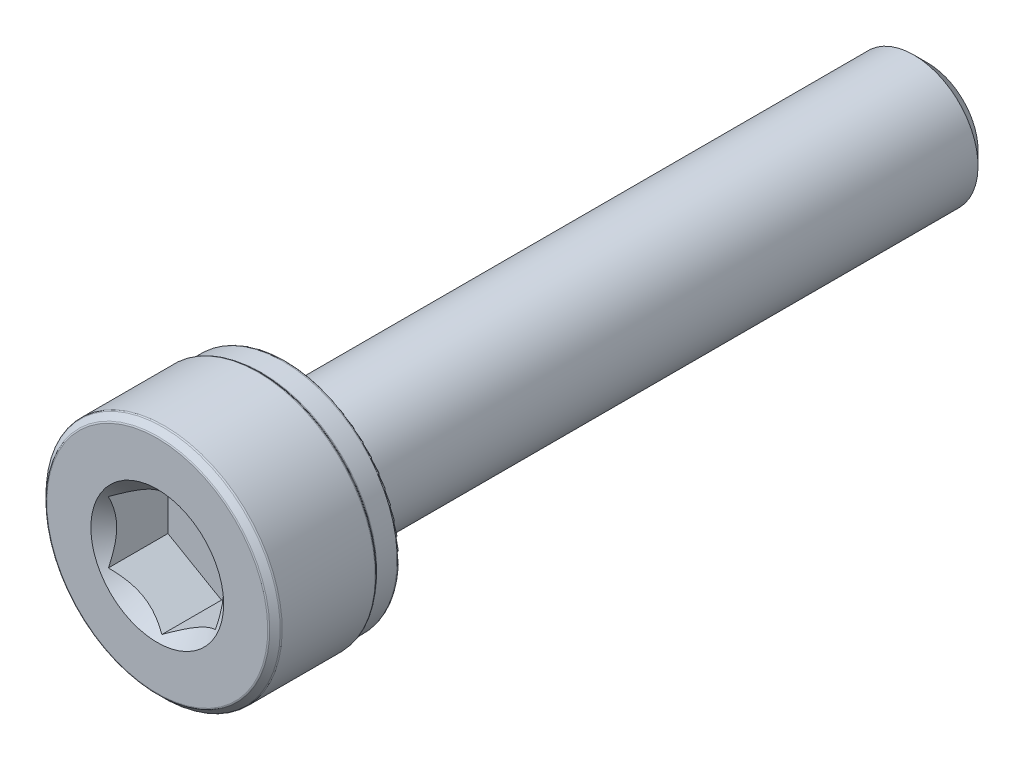
SolidWorks part; units mm, degrees
ref_plane "Front Plane" through (0, 0, 0) normal (0, 0, 1) x (1, 0, 0)
ref_plane "Top Plane" through (0, 0, 0) normal (0, 1, 0) x (1, 0, 0)
ref_plane "Right Plane" through (0, 0, 0) normal (1, 0, 0) x (0, 0, -1)
sketch "Sketch1" plane through (0, 0, 0) normal (1, 0, 0) x (0, 0, -1)
  line L0 (-9, 0) -> (9, 0) construction
  line L1 (9, 0) -> (9, 1.1752) construction
  line L2 (9, 1.1752) -> (8.6752, 1.5) construction
  line L3 (8.6752, 1.5) -> (8.625, 1.5) construction
  line L4 (8.625, 1.5) -> (-6, 1.5) construction
  line L5 (-6, 1.5) -> (-6, 2.75) construction
  line L6 (-6, 2.75) -> (-9, 2.75) construction
  line L7 (-9, 2.75) -> (-9, 0) construction
  line L8 (9, 1.1752) -> (9, 1.5) construction
  line L9 (8.9688, 1.5541) -> (9.2188, 1.1211) construction
  line L10 (9.2188, 1.1211) -> (9.4688, 1.5541) construction
  line L11 (9.4688, 1.5541) -> (8.9688, 1.5541) construction
  line L12 (9.2188, 1.5541) -> (9.2188, 1.5) construction
  line L13 (9.2188, 1.1211) -> (9.2188, 1.1752) construction
  line L14 (9.1875, 1.1752) -> (9.25, 1.1752) construction
  line L15 (9, 1.5) -> (9.4375, 1.5) construction
  line L16 (8.9844, 1.5271) -> (9.4531, 1.5271) construction
  line L17 (9, 0) -> (9, -1.5) construction
  line L18 (-6.15, 2.75) -> (-6, 2.6) construction
  line L19 (-8.85, 2.75) -> (-9, 2.6) construction
  line L20 (-6, 1.5) -> (-6, 0) construction
  line L21 (-6, 0.75) -> (-1, 0.75) construction
  line L22 (-1, 0.75) -> (4, 0.75) construction
  line L23 (4, 0.75) -> (9, 0.75) construction
  line L24 (-1, 0.75) -> (-1, 1.5) construction
  line L25 (-1, 1.5) -> (-1, 2.75) construction
  line L26 (4, 0.75) -> (4, 2.75) construction
  point P0 (-9, 1.25)
  point P3 (7.75, 1.5)
  point P4 (0, 0)
  point P18 (4, 1.5)
  point P22 (9.2188, 1.1752)
  point P24 (8.625, 1.5)
  point P25 (9.2188, 1.5)
  point P28 (9.2188, 1.5271)
  point P29 (7.75, -1.5)
  point P30 (-1, 1.5)
  point P31 (-7.5, 2.75)
  point P37 (-6.525, 2.75)
  point P38 (-8.775, 2.75)
  point P45 (-1, 0.75)
  point P46 (4, 0.75)
  dimension "D1" = 45
  dimension "D2" = 0.0625
  dimension "D7" = 0.15
  dimension "D8" = 0.15
  dimension "D9" = 0.15
  dimension "D10" = 0.075
  dimension "D11" = 0.375
  dimension "Drive Size" = 2.5
  dimension "Head Diameter" = 5.5
  dimension "Head Height" = 3
  dimension "Thread Pitch" = 0.5
  dimension "Thread Dia" = 3
  dimension "Length" = 15
  dimension "D12" = 0.375
  dimension "D4" = 1.25
  dimension "Key Engagement" = 1.5
sketch "Sketch2" plane through (0, 0, 0) normal (1, 0, 0) x (0, 0, -1)
  line L0 (-9, 0) -> (-9, 2.5806)
  line L1 (-8.8306, 2.75) -> (-6.6569, 2.75)
  line L2 (-6, 2.6062) -> (-6, 1.65)
  line L4 (8.6752, 1.5) -> (9, 1.1752)
  line L5 (9, 1.1752) -> (9, 0)
  line L6 (-6, 2.75) -> (-9, 2.75) construction
  line L7 (9, 0) -> (-9, 0)
  line L8 (-8.85, 2.75) -> (-9, 2.6) construction
  line L10 (-8.8637, 2.7363) -> (-8.9863, 2.6137)
  line L12 (-6.5431, 2.675) -> (-6.0688, 2.675)
  line L14 (-6.15, 2.75) -> (-6, 2.6) construction
  line L15 (-6.6238, 2.7363) -> (-6.5762, 2.6887)
  line L17 (-6, 1.5) -> (-6, 2.75) construction
  line L19 (-5.85, 1.5) -> (8.6752, 1.5)
  line L20 (8.625, 1.5) -> (-6, 1.5) construction
  arc A0 (-6.0688, 2.675) -> (-6, 2.6062) centre (-6.0688, 2.6062) cw
  arc A1 (-6, 1.65) -> (-5.85, 1.5) centre (-5.85, 1.65) ccw
  arc A2 (-8.8637, 2.7363) -> (-8.8306, 2.75) centre (-8.8306, 2.7031) cw
  arc A3 (-8.9863, 2.6137) -> (-9, 2.5806) centre (-8.9531, 2.5806) ccw
  arc A4 (-6.6238, 2.7363) -> (-6.6569, 2.75) centre (-6.6569, 2.7031) ccw
  arc A5 (-6.5762, 2.6887) -> (-6.5431, 2.675) centre (-6.5431, 2.7219) ccw
  point P22 (-6.075, 2.675)
  point P37 (-6.5625, 2.675)
  dimension "D2" = 0.0688
  dimension "D3" = 0.15
  dimension "D4" = 0.0469
  dimension "D1" = 0.5625
revolve "Revolve1" add sketch "Sketch2" angle 360 about L7
sketch "Sketch3" plane through (0, 0, 9) normal (0, 0, 1) x (1, 0, 0)
  line L1 (1.25, -0.7217) -> (1.25, 0.7217)
  line L2 (1.25, 0.7217) -> (0, 1.4434)
  line L3 (0, 1.4434) -> (-1.25, 0.7217)
  line L4 (-1.25, 0.7217) -> (-1.25, -0.7217)
  line L5 (-1.25, -0.7217) -> (0, -1.4434)
  line L6 (0, -1.4434) -> (1.25, -0.7217)
  circle A0 centre (0, 0) radius 1.25 construction
  circle A1 centre (0, 0) radius 2.75 construction
  circle A2 centre (0, 0) radius 2.75 construction
  circle A3 centre (0, 0) radius 1.4434 construction
  dimension "D1" = 2.8868
extrude "Cut-Extrude1" cut sketch "Sketch3" against normal up to vertex (1.5 mm away) up to point (0, 2.75, 7.5)
sketch "Sketch4" plane through (0, 0, 9) normal (0, 0, 1) x (1, 0, 0)
  circle A0 centre (0, 0) radius 1.5516
  dimension "D1" = 3.1033
extrude "Cut-Extrude2" cut sketch "Sketch4" against normal up to vertex (1.5 mm away) draft 45 up to point (0, 2.75, 7.5)
sketch "Sketch6" [suppressed] plane through (0, 0, -9) normal (0, 0, -1) x (-1, 0, 0)
  circle A0 centre (0, 0) radius 1.5
curve "Helix/Spiral1" [suppressed] pitch 0.5 height 15.5 turns 31
sketch "Sketch7" [suppressed] plane through (0, 0, 0) normal (1, 0, 0) x (0, 0, -1)
  line L0 (8.9844, 1.5271) -> (9.4531, 1.5271)
  line L1 (9.4531, 1.5271) -> (9.25, 1.1752)
  line L2 (9.25, 1.1752) -> (9.1875, 1.1752)
  line L3 (9.1875, 1.1752) -> (8.9844, 1.5271)
sweep "Cut-Sweep1" [suppressed] cut profiles "Sketch7" path "Helix/Spiral1"
sketch "Sketch8" [suppressed] plane through (0, 0, 0) normal (1, 0, 0) x (0, 0, -1)
  line L0 (-7.5, 0) -> (-7.5, 1.65)
  line L1 (-7.5, 0.7217) -> (-7.5, 1.4434) construction
  line L2 (-5.85, 1.5) -> (-5.75, 1.5)
  line L3 (-6, 1.65) -> (-7.5, 1.65)
  line L4 (-5.75, 1.5) -> (-4.884, 0)
  line L5 (-4.884, 0) -> (-7.5, 0)
  line L7 (-9, 0) -> (9, 0) construction
  line L8 (-6, 1.5) -> (-6, 2.75) construction
  arc A0 (-6, 1.65) -> (-5.85, 1.5) centre (-5.85, 1.65) ccw construction
  arc A1 (-6, 1.65) -> (-5.85, 1.5) centre (-5.85, 1.65) ccw
  dimension "D1" = 60
  dimension "D2" = 0.25
revolve "Revolve2" [suppressed] add sketch "Sketch8" angle 360 about L5
sketch "Sketch9" [suppressed] plane through (0, 0, 9) normal (0, 0, 1) x (1, 0, 0)
  line L0 (-0.0125, 2.703) -> (-0.0688, 2.8285)
  line L1 (-0.0688, 2.8285) -> (0.0687, 2.8285)
  line L2 (0.0687, 2.8285) -> (0.0125, 2.703)
  line L3 (0, 2.75) -> (0, 2.6) construction
  line L4 (0, 0) -> (-0.0688, 2.8285) construction
  line L5 (0.0687, 2.8285) -> (0, 0) construction
  circle A0 centre (0, 0) radius 2.675 construction
  arc A4 (-0.0125, 2.703) -> (0.0125, 2.703) centre (0, 2.7086) ccw
  point P10 (0, 2.675)
  point P19 (0, 2.675)
  dimension "D2" = 0.0138
  dimension "D1" = 0.1375
  dimension "D3" = 2.785
extrude "Cut-Extrude3" [suppressed] cut sketch "Sketch9" against normal through all
pattern_circular "CirPattern1" [suppressed] count 80 over 360 of bodies 112
equation "\"D2@Sketch1\" = \"Thread Pitch@Sketch1\" / 8"
equation "\"D4@Helix/Spiral1\" = \"Thread Pitch@Sketch1\""
equation "\"D7@Sketch1\" = \"Head Height@Sketch1\" * .05"
equation "\"D8@Sketch1\"=\"D7@Sketch1\""
equation "\"D9@Sketch1\"=\"D7@Sketch1\""
equation "\"D10@Sketch1\"=\"D7@Sketch1\"/2"
equation "\"D11@Sketch1\"=\"D10@Sketch1\"*5"
equation "\"D4@Sketch1\"=\"Thread Pitch@Sketch1\"*2.5"
equation "\"D12@Sketch1\"=\"Thread Pitch@Sketch1\"*.75"
equation "\"D3@Helix/Spiral1\"=\"Length@Sketch1\"+\"Thread Pitch@Sketch1\""
equation "\"D1@Sketch2\"=\"Head Height@Sketch1\"*0.1875"
equation "\"D2@Sketch2\"=\"Head Diameter@Sketch1\"*0.0125"
equation "\"D3@Sketch2\"=\"Thread Dia@Sketch1\"*0.05"
equation "\"D1@Sketch9\"=\"Head Diameter@Sketch1\"*0.025"
equation "\"D2@Sketch9\"=\"D1@Sketch9\"*0.1"
equation "\"D2@Sketch8\"=\"Thread Pitch@Sketch1\"*00.5"
equation "\"D4@Sketch2\"=\"D8@Sketch1\"*0.3125"
equation "\"D1@CirPattern1\"=int ((360/\"D3@Sketch9\")*0.625)"
equation "\"D1@Sketch4\"=\"D1@Sketch3\" * 01.075"
